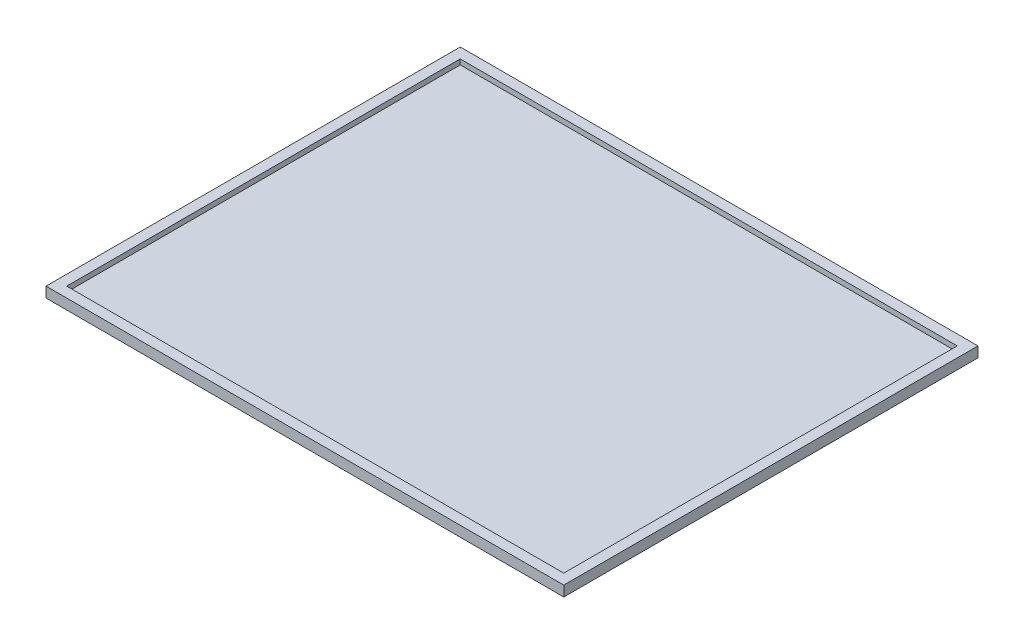
SolidWorks part; units mm, degrees
ref_plane "Front" through (0, 0, 0) normal (0, 0, 1) x (1, 0, 0)
ref_plane "Top" through (0, 0, 0) normal (0, 1, 0) x (1, 0, 0)
ref_plane "Right" through (0, 0, 0) normal (1, 0, 0) x (0, 0, -1)
sketch "Sketch1" plane through (0, 0, 0) normal (0, 1, 0) x (1, 0, 0)
  line L0 (-240, -190) -> (-240, 190)
  line L1 (-250, -200) -> (250, -200)
  line L2 (-250, -200) -> (-250, 200)
  line L3 (-250, 200) -> (250, 200)
  line L4 (250, -200) -> (250, 200)
  line L5 (-250, -200) -> (250, 200) construction
  line L6 (-250, 200) -> (250, -200) construction
  line L7 (-240, 190) -> (240, 190)
  line L8 (240, -190) -> (240, 190)
  line L9 (-240, -190) -> (240, -190)
  point P0 (0, 0)
  dimension "D1" = 500
  dimension "D2" = 400
  dimension "D3" = 10
extrude "Boss-Extrude1" add sketch "Sketch1" along normal blind 10
extrude "Boss-Extrude3" add sketch "Sketch1<3>" along normal blind 5 contours L0 L9 L8 L7 region at (0, 0, 0)
sketch "Sketch1<3>" plane through (0, 0, 0) normal (0, 1, 0) x (1, 0, 0) same geometry as "Sketch1"
